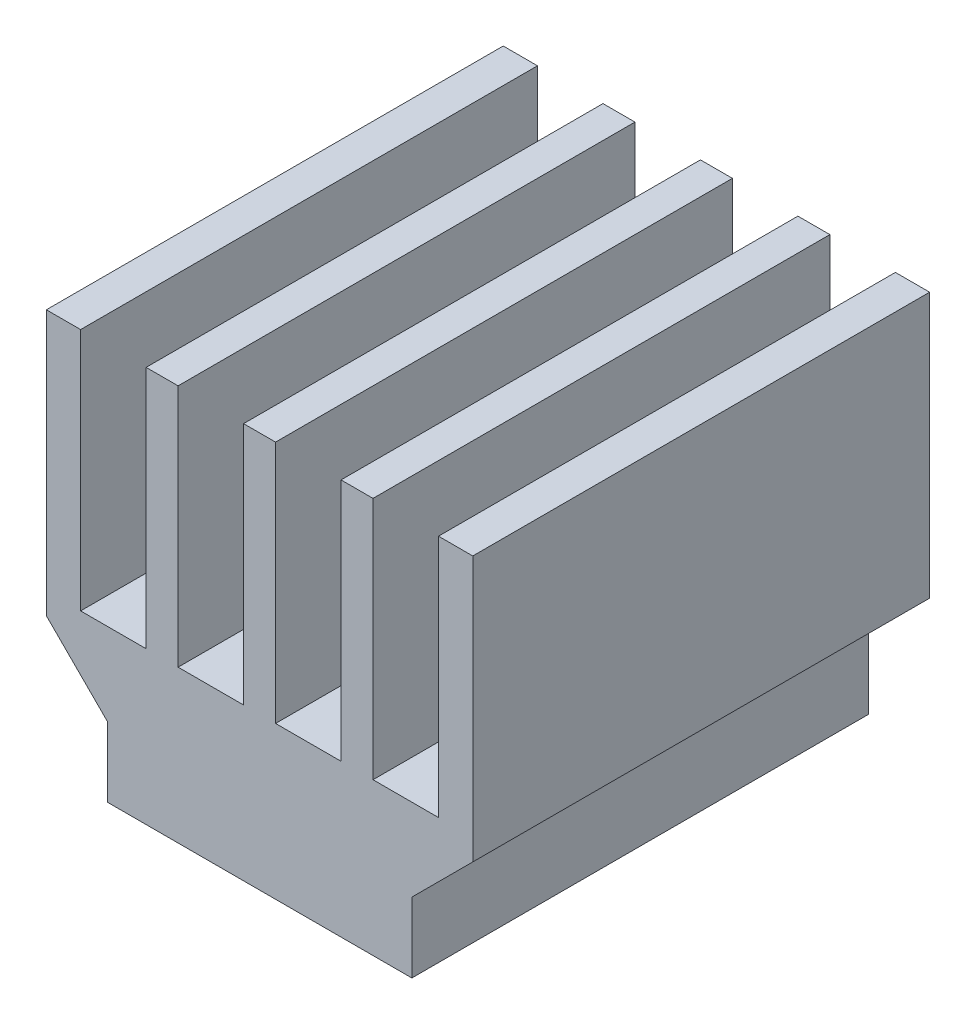
SolidWorks part; units mm, degrees
material "6061-T6 (SS)"
ref_plane "Front Plane" through (0, 0, 0) normal (0, 0, 1) x (1, 0, 0)
ref_plane "Top Plane" through (0, 0, 0) normal (0, 1, 0) x (1, 0, 0)
ref_plane "Right Plane" through (0, 0, 0) normal (1, 0, 0) x (0, 0, -1)
sketch "Sketch1" plane through (0, 0, 0) normal (0, 0, 1) x (1, 0, 0)
  line L0 (-7, 13) -> (-7, 0)
  line L1 (-7, 13) -> (7, 13)
  line L2 (-7, 0) -> (7, 0)
  line L3 (7, 13) -> (7, 0)
  line L4 (-7, 13) -> (7, 0) construction
  line L5 (-7, 0) -> (7, 13) construction
  line L6 (7, 4.3) -> (5, 2.3)
  line L7 (5, 2.3) -> (5, 0)
  line L8 (0, 13) -> (0, 0) construction
  line L9 (-0.525, 13) -> (-0.525, 5)
  line L10 (0.525, 13) -> (2.675, 13)
  line L11 (0.525, 13) -> (0.525, 5)
  line L12 (0.525, 5) -> (2.675, 5)
  line L13 (2.675, 13) -> (2.675, 5)
  line L14 (3.725, 13) -> (5.875, 13)
  line L15 (3.725, 13) -> (3.725, 5)
  line L16 (3.725, 5) -> (5.875, 5)
  line L17 (5.875, 13) -> (5.875, 5)
  line L18 (-0.525, 5) -> (-2.675, 5)
  line L19 (-2.675, 13) -> (-2.675, 5)
  line L20 (-3.725, 13) -> (-3.725, 5)
  line L21 (-3.725, 5) -> (-5.875, 5)
  line L22 (-5.875, 13) -> (-5.875, 5)
  line L23 (-5, 2.3) -> (-5, 0)
  line L24 (-7, 4.3) -> (-5, 2.3)
  point P1 (0, 6.5)
  point P3 (0, 0)
  dimension "D1" = 14
  dimension "D2" = 13
  dimension "D3" = 4.3
  dimension "D5" = 135
  dimension "D4" = 2
  dimension "D6" = 2.15
  dimension "D7" = 0.525
  dimension "D8" = 8
  dimension "D9" = 1.05
  dimension "D10" = 2.15
extrude "Boss-Extrude1" add sketch "Sketch1" along normal blind 15 contours L0 L24 L23 L2 L7 L6 L3 L1 L17 L16 L15 L13 L12 L11 L9 L18 L19 L20 L21 L22 region at (0, 5.4135, 0)
equation "\"D10@Sketch1\"=\"D6@Sketch1\""
